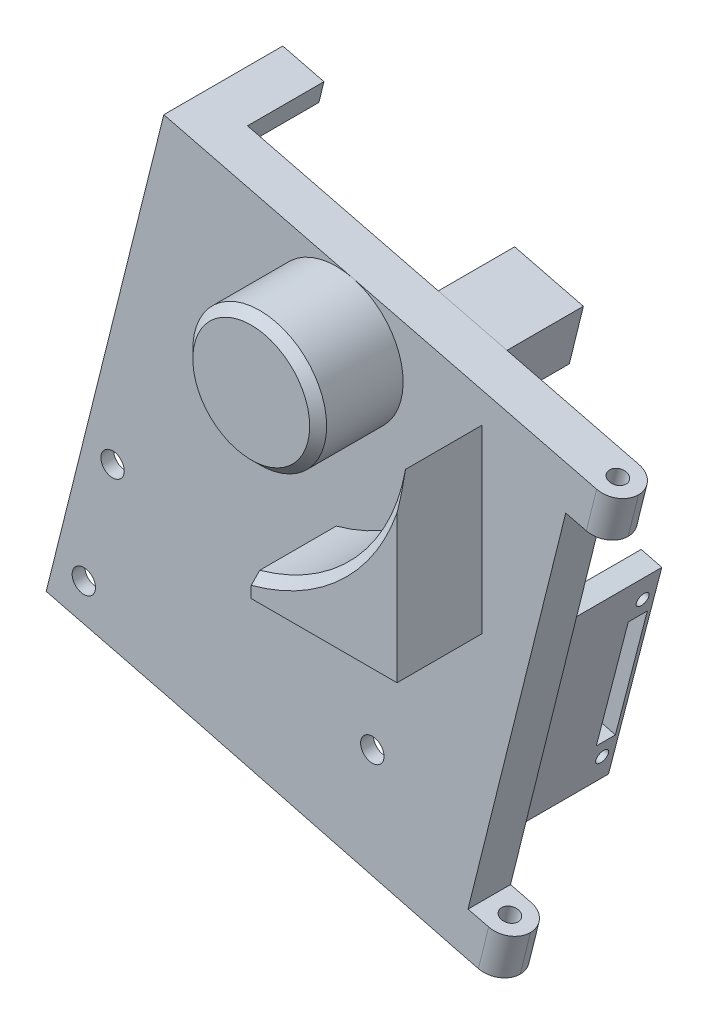
SolidWorks part; units mm, degrees
ref_plane "정면" through (0, 0, 0) normal (1, 0, 0) x (0, 1, 0)
ref_plane "윗면" through (0, 0, 0) normal (0, 0, 1) x (0, 1, 0)
ref_plane "우측면" through (0, 0, 0) normal (0, 1, 0) x (-1, 0, 0)
sketch "스케치1" plane through (0, 0, 0) normal (0, 0, 1) x (0, 1, 0)
  line L2 (-37.227, 0) -> (-42, 0)
  line L12 (-42, 30) -> (18, 30)
  line L13 (-42, 30) -> (-42, -34.3163)
  line L14 (-42, -34.3163) -> (18, -34.3163)
  line L15 (18, 30) -> (18, -34.3163)
  circle A0 centre (0, 0) radius 15.75
  arc A1 (-37.227, 0) -> (0.5011, -34.3163) centre (9, 12.9253) ccw
  dimension "D1" = 31.5
  dimension "D4" = 48
  dimension "D5" = 30
  dimension "D6" = 60
extrude "보스-돌출1" add sketch "스케치1" along normal blind 20 contours A0 | A1 L2 L13 L14 region at (22.8039, -30.9995, 0) region at (0, 0, 0)
sketch "스케치2" plane through (0, 0, 0) normal (0, 0, -1) x (1, 0, 0)
  line L0 (-15.75, -42) -> (43, -42)
  line L1 (-15.75, 42) -> (-15.75, -42)
  line L10 (43, -42) -> (43, 42)
  line L11 (-15.75, 42) -> (43, 42)
sketch "스케치17" plane through (0, 0, 0) normal (0, 0, -1) x (-1, 0, 0)
  line L0 (-56.4488, 2.1579) -> (-37.0309, -75.723)
  line L2 (30.8898, -58.7884) -> (11.4719, 19.0924)
  line L3 (11.4719, 19.0924) -> (-56.4488, 2.1579)
  line L4 (15.75, -42) -> (15.75, 42) construction
  line L5 (-37.0309, -75.723) -> (-28.6118, -109.4904)
  line L7 (30.8898, -58.7884) -> (39.1521, -91.9269)
  line L8 (-28.6118, -109.4904) -> (39.1521, -91.9269)
  circle A2 centre (0, 0) radius 15.75 construction
  dimension "D1" = 14
  dimension "D2" = 70
extrude "보스-돌출5" add sketch "스케치17" along normal blind 10
chamfer "모따기3" distance 2 angle 45 2 edges at (22.5834, -23.2976, 20) (15.75, 0, 20)
sketch "스케치18" plane through (52.6385, -13.1243, 0) normal (0.9703, -0.2419, 0) x (0.2419, 0.9703, 0)
  line L0 (15.75, 0) -> (-99.3163, 0) construction
  line L1 (-99.3163, -10) -> (-89.3163, -10)
  line L2 (-99.3163, -10) -> (-99.3163, 0)
  line L3 (-99.3163, 0) -> (-89.3163, 0)
  line L4 (-89.3163, -10) -> (-89.3163, 0)
  line L5 (-44.5627, 0) -> (36.9422, 0) construction
  line L6 (15.75, -10) -> (5.75, -10)
  line L7 (15.75, -10) -> (15.75, 0)
  line L8 (15.75, 0) -> (5.75, 0)
  line L9 (5.75, -10) -> (5.75, 0)
  dimension "D1" = 10
  dimension "D2" = 10
extrude "보스-돌출6" add sketch "스케치18" along normal blind 10
sketch "스케치19" plane through (-24.0268, -96.3662, 0) normal (-0.2419, -0.9703, 0) x (0.9703, -0.2419, 0)
  circle A0 centre (59.25, -5) radius 2
  dimension "D3" = 4
extrude "컷-돌출1" cut sketch "스케치19" against normal through all both and the other way through all
fillet "필렛2" radius 5 4 edges at (64.9422, -5.1128, -10) (64.9422, -5.1128, 0) (39.5243, -107.0582, -10) (39.5243, -107.0582, 0)
sketch "스케치21" plane through (0, 0, -10) normal (0, 0, -1) x (1, 0, 0)
  line L0 (-11.4719, -19.0924) -> (-39.1521, 91.9269)
  line L1 (-11.4719, -19.0924) -> (-40.5808, -26.3501)
  line L2 (-39.1521, 91.9269) -> (-68.261, 84.6693)
  line L3 (-40.5808, -26.3501) -> (-68.261, 84.6693)
  dimension "D1" = 30
extrude "보스-돌출7" add sketch "스케치21" against normal blind 10
sketch "스케치22" plane through (0, 0, -10) normal (0, 0, -1) x (1, 0, 0)
  line L0 (-68.261, 84.6693) -> (-40.5808, -26.3501) construction
  line L1 (-68.261, 84.6693) -> (-57.3745, 41.006)
  line L3 (-57.3745, 41.006) -> (20.2492, 60.3597)
  line L4 (9.3627, 104.023) -> (20.2492, 60.3597)
  line L6 (9.3627, 104.023) -> (4.3745, 124.0294)
  line L7 (-68.261, 84.6693) -> (-73.2491, 104.6757)
  line L8 (4.3745, 124.0294) -> (-73.2491, 104.6757)
  dimension "D1" = 80
  dimension "D2" = 45
extrude "컷-돌출2" cut sketch "스케치22" against normal blind 7
sketch "스케치23" plane through (0, 0, -3) normal (0, 0, -1) x (1, 0, 0)
  circle A0 centre (8.4977, 78.5573) radius 2.75
  circle A1 centre (-52.6388, 50.9469) radius 2.75
  circle A2 centre (-59.4126, 78.1152) radius 2.75
  dimension "D11" = 5.5
  dimension "D12" = 5.5
  dimension "D13" = 5.5
extrude "컷-돌출3" cut sketch "스케치23" against normal blind 7
sketch "스케치27" plane through (0, 0, -10) normal (0, 0, -1) x (1, 0, 0)
  line L4 (-57.3745, 41.006) -> (-40.5808, -26.3501) construction
  line L7 (-43, -16.6471) -> (-38.1485, -15.4375)
  line L8 (-36.9389, -20.289) -> (-38.1485, -15.4375)
  line L11 (-36.9389, -20.289) -> (-32.0874, -19.0794)
  line L12 (-30.8778, -23.9309) -> (-32.0874, -19.0794)
  line L14 (-47.3415, 21.4337) -> (-42.4901, 22.6433)
  line L16 (-42.4901, 22.6433) -> (-43.6997, 27.4948)
  line L19 (-50.9834, 15.3726) -> (-46.1319, 16.5822)
  line L20 (-47.3415, 21.4337) -> (-46.1319, 16.5822)
  line L34 (1.2216, 38.6949) -> (17.429, 42.7359)
  line L39 (-53.4026, 25.0756) -> (-50.9834, 15.3726)
  line L40 (-53.4026, 25.0756) -> (-43.6997, 27.4948)
  line L41 (-43, -16.6471) -> (-40.5808, -26.3501)
  line L42 (-40.5808, -26.3501) -> (-30.8778, -23.9309)
  line L51 (13.7871, 36.6748) -> (2.4312, 33.8435)
  line L52 (1.2216, 38.6949) -> (2.4312, 33.8435)
  line L59 (13.7871, 36.6748) -> (16.0569, 27.5712)
  line L75 (26.8707, 4.7245) -> (22.0192, 3.5149)
  line L76 (22.0192, 3.5149) -> (24.1487, -5.0262)
  line L78 (30.1758, -8.6766) -> (26.8707, 4.7245)
  line L79 (12.7929, -7.8575) -> (24.1487, -5.0262)
  line L80 (12.7929, -7.8575) -> (14.0025, -12.709)
  line L81 (14.0025, -12.709) -> (30.1758, -8.6766)
  line L82 (17.429, 42.7359) -> (20.9083, 28.7809)
  line L83 (16.0569, 27.5712) -> (20.9083, 28.7809)
  dimension "D3" = 5
  dimension "D4" = 5
  dimension "D5" = 5
  dimension "D7" = 5
  dimension "D8" = 10
extrude "보스-돌출9" add sketch "스케치27" along normal blind 18
fillet "필렛3" radius 2.5 4 edges at (-47.3415, -21.4337, -19) (-36.9389, 20.289, -19) (24.1487, 5.0262, -19) (13.7871, -36.6748, -19)
sketch "스케치28" plane through (-24.791, -95.6491, 0) normal (-0.2509, -0.968, 0) x (0.968, -0.2509, 0)
  line L1 (35.1665, -10) -> (40.1665, -10)
  line L2 (35.1665, -10) -> (35.1665, -50)
  line L3 (35.1665, -50) -> (40.1665, -50)
  line L4 (40.1665, -10) -> (40.1665, -50)
  dimension "D1" = 40
  dimension "D2" = 5
extrude "보스-돌출10" add sketch "스케치28" against normal blind 50
sketch "스케치29" plane through (38.8817, -10.0776, 0) normal (0.968, -0.2509, 0) x (0.2509, 0.968, 0)
  line L0 (-48.8097, -50) -> (-98.8097, -50) construction
  line L1 (-48.8097, -10) -> (-98.8097, -10) construction
  line L8 (-98.8097, -50) -> (-98.8097, -10) construction
  line L13 (-58.8097, -49.1109) -> (-88.8097, -49.1109)
  line L14 (-58.8097, -49.1109) -> (-58.8097, -44.6162)
  line L15 (-58.8097, -44.6162) -> (-88.8097, -44.6162)
  line L16 (-88.8097, -49.1109) -> (-88.8097, -44.6162)
  circle A0 centre (-54.8097, -47) radius 1.5
  circle A1 centre (-92.8097, -47) radius 1.5
  circle A2 centre (-92.8097, -13) radius 1.5
  circle A3 centre (-54.8097, -13) radius 1.5
  dimension "D6" = 3
  dimension "D7" = 3
  dimension "D8" = 3
  dimension "D9" = 3
  dimension "D1" = 40
  dimension "D2" = 30
  dimension "D3" = 10
  dimension "D4" = 38
  dimension "D5" = 34
extrude "컷-돌출4" cut sketch "스케치29" against normal blind 50
